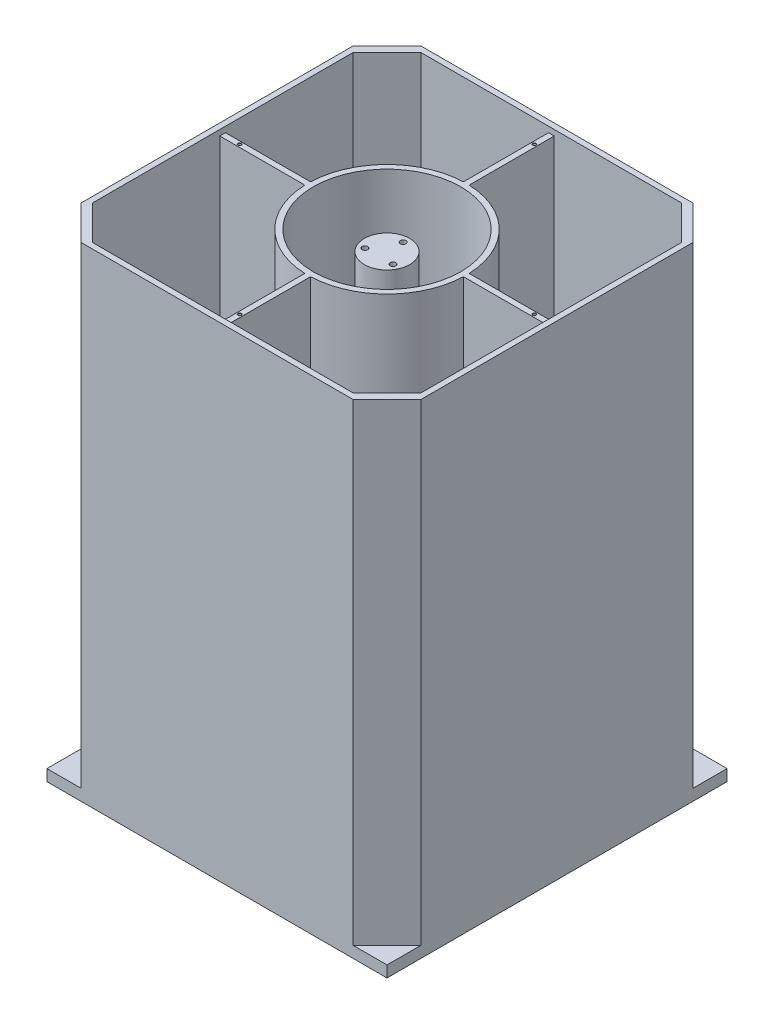
SolidWorks part; units mm, degrees
ref_plane "Front Plane" through (0, 0, 0) normal (0, 0, 1) x (1, 0, 0)
ref_plane "Top Plane" through (0, 0, 0) normal (0, 1, 0) x (1, 0, 0)
ref_plane "Right Plane" through (0, 0, 0) normal (1, 0, 0) x (0, 0, -1)
sketch "Sketch1" plane through (0, 0, 0) normal (0, 1, 0) x (1, 0, 0)
  line L1 (-150, 150) -> (150, 150)
  line L2 (-150, 150) -> (-150, -150)
  line L3 (-150, -150) -> (150, -150)
  line L4 (150, 150) -> (150, -150)
  line L5 (-150, 150) -> (150, -150) construction
  line L6 (-150, -150) -> (150, 150) construction
  circle A0 centre (0, 0) radius 65
  circle A1 centre (0, 0) radius 62.5
  circle A2 centre (0, 0) radius 70
  circle A3 centre (0, 0) radius 55
  circle A4 centre (0, 0) radius 20
  circle A5 centre (0, 0) radius 17.5
  point P0 (0, 0)
  dimension "D3" = 130
  dimension "D4" = 125
  dimension "D5" = 140
  dimension "D6" = 110
  dimension "D7" = 40
  dimension "D8" = 35
  dimension "D1" = 300
  dimension "D2" = 300
extrude "Boss-Extrude1" add sketch "Sketch1" along normal blind 10 contours L4 L1 L2 L3 A2 | A3 A4 | A4 A5 | A1 A3 | A0 A1 | A2 A0 region at (0, 0, -145.7574) region at (-63.1615, 0, 0) region at (-60.7322, 0, 0) region at (-68.0201, 0, 0) region at (-53.4444, 0, 0) region at (-19.4343, 0, 0)
extrude "Boss-Extrude2" add sketch "Sketch1<3>" along normal blind 292 contours A0 A1 region at (-63.1615, 0, 0)
sketch "Sketch1<3>" plane through (0, 0, 0) normal (0, 1, 0) x (1, 0, 0) same geometry as "Sketch1"
extrude "Boss-Extrude3" add sketch "Sketch1<4>" along normal blind 422 contours A2 A0 region at (-68.0201, 0, 0)
sketch "Sketch1<4>" plane through (0, 0, 0) normal (0, 1, 0) x (1, 0, 0) same geometry as "Sketch1"
extrude "Boss-Extrude4" add sketch "Sketch1<5>" along normal blind 405 contours A4 A5 region at (-19.4343, 0, 0)
sketch "Sketch1<5>" plane through (0, 0, 0) normal (0, 1, 0) x (1, 0, 0) same geometry as "Sketch1"
ref_plane "Plane1" through (0, 405, 0) normal (0, 1, 0) x (1, 0, 0)
sketch "Sketch3" plane through (0, 405, 0) normal (0, 1, 0) x (1, 0, 0)
  circle A0 centre (0, 0) radius 20
extrude "Boss-Extrude5" add sketch "Sketch3" against normal blind 5
sketch "Sketch4" plane through (0, 405, 0) normal (0, 1, 0) x (1, 0, 0)
  line L0 (0, 0) -> (0, 40.2614) construction
  circle A0 centre (0, 14.25) radius 2.5
  circle A1 centre (12.3409, -7.125) radius 2.5
  circle A2 centre (-12.3409, -7.125) radius 2.5
  point P3 (0, 14.25)
  point P12 (0, 0)
  dimension "D2" = 5
  dimension "D1" = 14.25
  dimension "D3" = 3
extrude "Cut-Extrude1" cut sketch "Sketch4" against normal blind 5
sketch "Sketch6" plane through (0, 0, 0) normal (0, 1, 0) x (1, 0, 0)
  line L0 (115, 145) -> (145, 115)
  line L1 (-120, 150) -> (120, 150)
  line L2 (-150, 120) -> (-150, -120)
  line L3 (-120, -150) -> (120, -150)
  line L4 (150, 120) -> (150, -120)
  line L5 (-150, 150) -> (150, -150) construction
  line L6 (-150, -150) -> (150, 150) construction
  line L7 (-115, 145) -> (115, 145)
  line L8 (-145, 115) -> (-145, -115)
  line L9 (-115, -145) -> (115, -145)
  line L10 (145, 115) -> (145, -115)
  line L11 (-145, 145) -> (145, -145) construction
  line L12 (-145, -145) -> (145, 145) construction
  line L13 (120, 150) -> (150, 120)
  line L14 (115, -145) -> (145, -115)
  line L15 (150, -120) -> (120, -150)
  line L16 (-145, -115) -> (-115, -145)
  line L17 (-150, -120) -> (-120, -150)
  line L18 (-145, 115) -> (-115, 145)
  line L19 (-150, 120) -> (-120, 150)
  point P1 (0, 0)
  point P7 (0, 0)
  dimension "D1" = 290
extrude "Boss-Extrude6" add sketch "Sketch6" along normal blind 427
ref_plane "Plane2" through (0, 422, 0) normal (0, 1, 0) x (1, 0, 0)
sketch "Sketch7" plane through (0, 422, 0) normal (0, 1, 0) x (1, 0, 0)
  line L0 (67.9707, 0) -> (145, 0)
  line L1 (145, 115) -> (145, -115) construction
  line L2 (-67.3883, 0) -> (-145, 0)
  line L3 (-145, 115) -> (-145, -115) construction
  line L4 (0, 67.648) -> (0, 145)
  line L5 (115, 145) -> (-115, 145) construction
  line L6 (0, -67.2909) -> (0, -145)
  line L7 (115, -145) -> (-115, -145) construction
  point P2 (0, -67.2909)
  point P20 (0, 0)
  point P21 (-67.3883, 0)
  point P23 (0, 0)
  point P24 (67.9707, 0)
  point P25 (0, 0)
  point P26 (0, 67.648)
  point P27 (0, 0)
rib "Rib3" sketch "Sketch7" sketch "Sketch7" thickness 5 extrusion direction normal to sketch draft on no parameters "D1"=5
sketch "Sketch8" plane through (0, 422, 0) normal (0, 1, 0) x (1, 0, 0)
  line L0 (0, 0) -> (0, 164.7241) construction
  circle A0 centre (0, 130) radius 1.5
  point P3 (0, 130)
  dimension "D2" = 3
  dimension "D1" = 130
hole_wizard "M3 Tapped Hole1" positions "Sketch9" profile "Sketch10" tap size "M3" standard "ISO"
sketch "Sketch9" plane through (0, 422, 0) normal (0, 1, 0) x (1, 0, 0)
  point P0 (0, 130)
  point P15 (130, 0)
  point P16 (0, -130)
  point P17 (-130, 0)
  dimension "D1" = 4
sketch "Sketch10" plane through (0, 422, -130) normal (1, 0, 0) x (0, 0, 1)
  line L0 (0, 0) -> (0, 8.2511)
  line L1 (0, 8.2511) -> (1.25, 7.5)
  line L2 (1.25, 7.5) -> (1.25, 0.275)
  line L3 (1.25, 0.275) -> (1.525, 0)
  line L5 (1.525, 0) -> (0, 0)
  line L6 (-1.25, 0.275) -> (-1.525, 0) construction
  line L10 (0, 8.2511) -> (-1.25, 7.5) construction
  line L11 (0, -6.35) -> (0, 107.95) construction
  dimension "Tap Drill Dia." = 2.5
  dimension "Tap Drill Depth" = 7.5
  dimension "Near C'Sink Dia." = 3.05
  dimension "Near C'Sink Angle" = 90
  dimension "Drill Angle" = 118
cosmetic thread "Hole Thread1" parameters "D1"=6, "D2"=3
cosmetic thread "Hole Thread2" parameters "D1"=6, "D2"=3
cosmetic thread "Hole Thread3" parameters "D1"=6, "D2"=3
cosmetic thread "Hole Thread4" parameters "D1"=6, "D2"=3
extrude "Boss-Extrude7" add sketch "Sketch1<6>" along normal blind 272 contours A1 A3 region at (-60.7322, 0, 0)
sketch "Sketch1<6>" plane through (0, 0, 0) normal (0, 1, 0) x (1, 0, 0) same geometry as "Sketch1"
